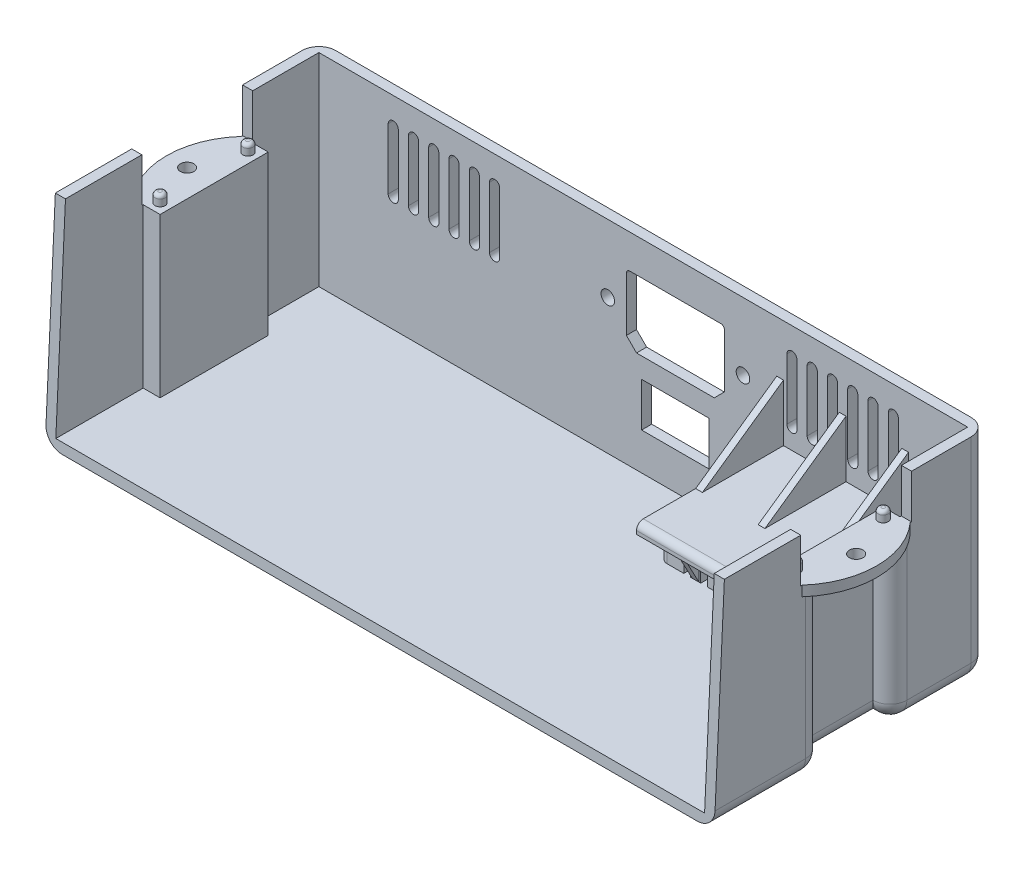
SolidWorks part; units mm, degrees
ref_plane "Alzado" through (0, 0, 0) normal (0, 0, 1) x (1, 0, 0)
ref_plane "Planta" through (0, 0, 0) normal (0, 1, 0) x (1, 0, 0)
ref_plane "Vista lateral" through (0, 0, 0) normal (1, 0, 0) x (0, 0, -1)
sketch "Croquis1" plane through (0, 0, 0) normal (0, 1, 0) x (1, 0, 0)
  line L0 (99, -10) -> (94, -10)
  line L1 (-99, 39) -> (99, 39)
  line L2 (-99, 39) -> (-99, 10)
  line L3 (-99, -42) -> (99, -42)
  line L4 (99, 39) -> (99, 10)
  line L5 (94, -10) -> (94, 10)
  line L6 (94, 10) -> (99, 10)
  line L7 (99, -10) -> (99, -42)
  line L8 (-99, 10) -> (-94, 10)
  line L9 (-94, 10) -> (-94, -10)
  line L10 (-94, -10) -> (-99, -10)
  line L11 (-99, -10) -> (-99, -42)
  point P4 (0, -42)
  point P7 (94, 0)
  point P14 (-94, 0)
  dimension "D1" = 81
  dimension "D2" = 198
  dimension "D3" = 39
  dimension "D4" = 5
  dimension "D5" = 20
  dimension "D6" = 20
  dimension "D7" = 5
extrude "Saliente-Extruir1" add sketch "Croquis1" along normal blind 3
sketch "Croquis2" plane through (0, 3, 0) normal (0, 1, 0) x (1, 0, 0)
  line L3 (96, 36) -> (-96, 36)
  line L4 (-96, 36) -> (-96, 16)
  line L6 (-99, 10) -> (-99, 39)
  line L7 (-99, 39) -> (99, 39)
  line L8 (99, 39) -> (99, 10)
  line L9 (-96, 16) -> (-91, 16)
  line L10 (-91, 16) -> (-91, -16)
  line L11 (-91, -16) -> (-96, -16)
  line L12 (-94, -10) -> (-99, -10)
  line L13 (-94, -10) -> (-94, 10)
  line L14 (-94, 10) -> (-99, 10)
  line L17 (91, 16) -> (96, 16)
  line L18 (91, 16) -> (91, -16)
  line L19 (91, -16) -> (96, -16)
  line L20 (96, 16) -> (96, 36)
  line L21 (99, 10) -> (94, 10)
  line L22 (94, 10) -> (94, -10)
  line L23 (94, -10) -> (99, -10)
  line L25 (96, -16) -> (96, -42)
  line L26 (-99, -42) -> (99, -42) construction
  line L27 (96, -42) -> (99, -42)
  line L28 (99, -42) -> (99, -10)
  line L29 (-96, -16) -> (-96, -42)
  line L30 (-96, -42) -> (-99, -42)
  line L31 (-99, -42) -> (-99, -10)
  dimension "D3" = 3
  dimension "D4" = 6
  dimension "D5" = 3
  dimension "D6" = 6
  dimension "D7" = 3
  dimension "D8" = 6
  dimension "D9" = 6
  dimension "D2" = 3
  dimension "D10" = 3
  dimension "D11" = 3
extrude "Saliente-Extruir2" add sketch "Croquis2" along normal blind 60
sketch "Croquis5" plane through (99, 0, 0) normal (1, 0, 0) x (0, 0, -1)
  line L2 (-42, 63) -> (-10, 63) construction
  line L3 (-39, 63) -> (-42, 63)
  line L5 (-42, 0) -> (-39, 63)
  line L6 (-42, 0) -> (-42, 63)
  dimension "D1" = 3
extrude "Cortar-Extruir2" cut sketch "Croquis5" against normal up to surface (198 mm away) up to face at (-99, 31.5, 26)
sketch "Croquis7" plane through (0, 63, 0) normal (0, 1, 0) x (1, 0, 0)
  line L0 (-91, -16) -> (-99, -16)
  line L1 (-99, -10) -> (-99, -39) construction
  line L2 (-99, -16) -> (-99, -10)
  line L3 (-99, -10) -> (-94, -10)
  line L4 (-94, -10) -> (-94, 10)
  line L5 (-94, 10) -> (-99, 10)
  line L6 (-99, 10) -> (-99, 16)
  line L7 (-99, 39) -> (-99, 10) construction
  line L8 (-99, 16) -> (-91, 16)
  line L9 (-91, 16) -> (-91, -16)
  line L10 (91, 16) -> (99, 16)
  line L11 (99, 10) -> (99, 39) construction
  line L12 (99, 16) -> (99, 10)
  line L13 (99, 10) -> (94, 10)
  line L14 (94, 10) -> (94, -10)
  line L15 (94, -10) -> (99, -10)
  line L16 (99, -10) -> (99, -16)
  line L17 (99, -39) -> (99, -10) construction
  line L18 (99, -16) -> (91, -16)
  line L20 (91, -16) -> (91, 16)
extrude "Cortar-Extruir3" cut sketch "Croquis7" against normal blind 16
sketch "Croquis8" plane through (0, 47, 0) normal (0, 1, 0) x (1, 0, 0)
  line L0 (-99, -16) -> (-91, -16)
  line L1 (-91, -16) -> (-91, 16)
  line L2 (-91, 16) -> (-99, 16)
  line L3 (99, -16) -> (91, -16)
  line L4 (91, -16) -> (91, 16)
  line L5 (91, 16) -> (99, 16)
  arc A0 (-99, -16) -> (-99, 16) centre (-81.1115, 0) cw
  arc A1 (99, -16) -> (99, 16) centre (81.1115, 0) ccw
  dimension "D1" = 24
  dimension "D2" = 24
extrude "Saliente-Extruir3" add sketch "Croquis8" along normal blind 3
sketch "Croquis9" plane through (0, 50, 0) normal (0, 1, 0) x (1, 0, 0)
  line L0 (-91, -16) -> (-91, 16) construction
  line L1 (91, 16) -> (91, -16) construction
  circle A0 centre (-99, 0) radius 2
  circle A1 centre (99, 0) radius 2
  dimension "D2" = 4
  dimension "D4" = 4
  dimension "D1" = 8
  dimension "D3" = 8
extrude "Cortar-Extruir4" cut sketch "Croquis9" against normal up to surface (3 mm away) up to face at (98.3519, 47, 0)
fillet "Redondeo1" radius 5 17 edges at (-99, 0, -24.5) (99, 0, -24.5) (-99, 31.5, -39) (99, 31.5, -39) (0, 0, -39) (99, 0, 26) (96.5, 0, 10) (94, 0, 0) (96.5, 0, -10) (-96.5, 0, -10) (-94, 0, 0) (-96.5, 0, 10) (-99, 0, 26) (99, 23.5, 10) (99, 23.5, -10) (-99, 23.5, 10) (-99, 23.5, -10)
sketch "Croquis10" plane through (0, 50, 0) normal (0, 1, 0) x (1, 0, 0)
  line L0 (96, 16) -> (91, 16) construction
  line L1 (91, 16) -> (91, -16) construction
  line L2 (91, -16) -> (96, -16) construction
  line L3 (-91, 16) -> (-96, 16) construction
  line L4 (-91, -16) -> (-91, 16) construction
  line L5 (-96, -16) -> (-91, -16) construction
  circle A0 centre (94, 13) radius 1.5
  circle A1 centre (94, -13) radius 1.5
  circle A2 centre (-94, 13) radius 1.5
  circle A3 centre (-94, -13) radius 1.5
  dimension "D1" = 3
  dimension "D3" = 3
  dimension "D5" = 3
  dimension "D7" = 3
  dimension "D6" = 3
  dimension "D9" = 3
  dimension "D10" = 3
  dimension "D2" = 3
  dimension "D4" = 3
  dimension "D8" = 3
  dimension "D11" = 3
  dimension "D12" = 3
extrude "Saliente-Extruir4" add sketch "Croquis10" along normal blind 3
fillet "Redondeo3" radius 1 4 edges at (-94, 53, 14.5) (-94, 53, -11.5) (94, 53, -11.5) (94, 53, 14.5)
sketch "Croquis11" plane through (0, 0, -39) normal (0, 0, -1) x (-1, 0, 0)
  line L0 (-72.5, 37) -> (-72.5, 55)
  line L1 (-75.5, 37) -> (-75.5, 55)
  line L2 (-94, 63) -> (94, 63) construction
  line L3 (-94, 63) -> (-94, 5) construction
  line L12 (-69.5, 37) -> (-69.5, 55)
  line L13 (-66.5, 37) -> (-66.5, 55)
  line L14 (-63.5, 37) -> (-63.5, 55)
  line L15 (-60.5, 37) -> (-60.5, 55)
  line L16 (-57.5, 37) -> (-57.5, 55)
  line L17 (-54.5, 37) -> (-54.5, 55)
  line L18 (-51.5, 37) -> (-51.5, 55)
  line L19 (-48.5, 37) -> (-48.5, 55)
  line L20 (-45.5, 37) -> (-45.5, 55)
  line L21 (-42.5, 37) -> (-42.5, 55)
  line L22 (0, 5) -> (0, 63) construction
  line L23 (-94, 5) -> (94, 5) construction
  line L24 (42.5, 37) -> (42.5, 55)
  line L25 (45.5, 37) -> (45.5, 55)
  line L26 (48.5, 37) -> (48.5, 55)
  line L27 (51.5, 37) -> (51.5, 55)
  line L28 (54.5, 37) -> (54.5, 55)
  line L29 (57.5, 37) -> (57.5, 55)
  line L30 (60.5, 37) -> (60.5, 55)
  line L31 (63.5, 37) -> (63.5, 55)
  line L32 (66.5, 37) -> (66.5, 55)
  line L33 (69.5, 37) -> (69.5, 55)
  line L34 (72.5, 37) -> (72.5, 55)
  line L35 (75.5, 37) -> (75.5, 55)
  arc A0 (-72.5, 37) -> (-75.5, 37) centre (-74, 37) cw
  arc A1 (-72.5, 55) -> (-75.5, 55) centre (-74, 55) ccw
  arc A10 (-66.5, 55) -> (-69.5, 55) centre (-68, 55) ccw
  arc A11 (-66.5, 37) -> (-69.5, 37) centre (-68, 37) cw
  arc A12 (-60.5, 55) -> (-63.5, 55) centre (-62, 55) ccw
  arc A13 (-60.5, 37) -> (-63.5, 37) centre (-62, 37) cw
  arc A14 (-54.5, 55) -> (-57.5, 55) centre (-56, 55) ccw
  arc A15 (-54.5, 37) -> (-57.5, 37) centre (-56, 37) cw
  arc A16 (-48.5, 55) -> (-51.5, 55) centre (-50, 55) ccw
  arc A17 (-48.5, 37) -> (-51.5, 37) centre (-50, 37) cw
  arc A18 (-42.5, 55) -> (-45.5, 55) centre (-44, 55) ccw
  arc A19 (-42.5, 37) -> (-45.5, 37) centre (-44, 37) cw
  arc A20 (42.5, 37) -> (45.5, 37) centre (44, 37) ccw
  arc A21 (42.5, 55) -> (45.5, 55) centre (44, 55) cw
  arc A22 (48.5, 37) -> (51.5, 37) centre (50, 37) ccw
  arc A23 (48.5, 55) -> (51.5, 55) centre (50, 55) cw
  arc A24 (54.5, 37) -> (57.5, 37) centre (56, 37) ccw
  arc A25 (54.5, 55) -> (57.5, 55) centre (56, 55) cw
  arc A26 (60.5, 37) -> (63.5, 37) centre (62, 37) ccw
  arc A27 (60.5, 55) -> (63.5, 55) centre (62, 55) cw
  arc A28 (66.5, 37) -> (69.5, 37) centre (68, 37) ccw
  arc A29 (66.5, 55) -> (69.5, 55) centre (68, 55) cw
  arc A30 (72.5, 37) -> (75.5, 37) centre (74, 37) ccw
  arc A31 (72.5, 55) -> (75.5, 55) centre (74, 55) cw
  dimension "D6" = 6
  dimension "D1" = 1.5
  dimension "D5" = 1.5
  dimension "D2" = 18
  dimension "D3" = 8
  dimension "D4" = 20
extrude "Cortar-Extruir5" cut sketch "Croquis11" against normal up to surface (3 mm away) up to face at (0, 33, -36)
sketch "Croquis13" plane through (0, 0, -39) normal (0, 0, -1) x (-1, 0, 0)
  line L0 (4, 53) -> (-23, 53)
  line L5 (5, 36) -> (5, 52)
  line L6 (-94, 63) -> (94, 63) construction
  line L8 (2, 33) -> (-21, 33)
  line L9 (-24, 36) -> (-24, 52)
  line L10 (10.5, 43) -> (-29.5, 43) construction
  line L11 (-9.5, 33) -> (-9.5, 53) construction
  line L12 (5, 36) -> (2, 33)
  line L13 (0.5, 14) -> (-19.5, 14)
  line L14 (0.5, 14) -> (0.5, 27)
  line L15 (0.5, 27) -> (-19.5, 27)
  line L16 (-19.5, 14) -> (-19.5, 27)
  line L17 (-21, 33) -> (-24, 36)
  circle A1 centre (-29.5, 43) radius 2
  circle A2 centre (10.5, 43) radius 2
  arc A3 (-42.5, 55) -> (-45.5, 55) centre (-44, 55) ccw construction
  arc A4 (4, 53) -> (5, 52) centre (4, 52) cw
  arc A5 (-23, 53) -> (-24, 52) centre (-23, 52) ccw
  point P13 (-9.5, 43)
  point P16 (-9.5, 43)
  point P21 (-9.5, 27)
  point P26 (5, 53)
  point P29 (-24, 53)
  dimension "D4" = 4
  dimension "D5" = 4
  dimension "D6" = 20
  dimension "D17" = 1
  dimension "D2" = 20
  dimension "D3" = 40
  dimension "D7" = 10
  dimension "D8" = 13
  dimension "D9" = 20
  dimension "D10" = 6
  dimension "D11" = 17
  dimension "D12" = 45
  dimension "D13" = 17
  dimension "D14" = 45
  dimension "D15" = 10
  dimension "D16" = 29
extrude "Cortar-Extruir6" cut sketch "Croquis13" against normal up to surface (3 mm away) up to face at (74, 46, -36)
sketch "Croquis15" plane through (0, 0, -39) normal (0, 0, -1) x (-1, 0, 0)
  line L0 (24.5, 18.5) -> (4.5, 18.5) construction
  line L1 (0.5, 14) -> (0.5, 27) construction
  line L3 (-19.5, 14) -> (0.5, 14) construction
  text T0 "POWER \r\nON" font "Century Gothic" height in points 14
  dimension "D1" = 4
  dimension "D2" = 20
  dimension "D3" = 4.5
extrude "Cortar-Extruir7" cut sketch "Croquis15" against normal blind 1
sketch "Croquis16" plane through (0, 0, -36) normal (0, 0, 1) x (1, 0, 0)
  line L0 (62, 37) -> (56, 37) construction
  line L1 (78.5, 28) -> (39.5, 28)
  line L2 (78.5, 28) -> (78.5, 31)
  line L3 (78.5, 31) -> (39.5, 31)
  line L4 (39.5, 28) -> (39.5, 31)
  line L5 (-96, 3) -> (96, 3) construction
  point P8 (59, 31)
  point P9 (59, 37)
  dimension "D2" = 3
  dimension "D1" = 39
  dimension "D3" = 25
extrude "Saliente-Extruir5" add sketch "Croquis16" along normal blind 34.5
sketch "Croquis19" plane through (0, 28, 0) normal (0, -1, 0) x (1, 0, 0)
  line L1 (39.5, -36) -> (78.5, -36) construction
  line L6 (61.5, -4.5) -> (74.5, -4.5)
  line L9 (78.5, -17.5) -> (78.5, -1.5)
  line L10 (78.5, -1.5) -> (39.5, -1.5)
  line L11 (61.5, -4.5) -> (61.5, -8.5)
  line L12 (39.5, -1.5) -> (39.5, -17.5)
  line L14 (39.5, -1.5) -> (78.5, -1.5) construction
  line L15 (42.5, -17.5) -> (42.5, -8.5)
  line L16 (43.5, -4.5) -> (56.5, -4.5)
  line L17 (57.5, -8.5) -> (57.5, -36)
  line L18 (75.5, -8.5) -> (75.5, -17.5)
  line L19 (61.5, -8.5) -> (60.5, -8.5)
  line L20 (57.5, -8.5) -> (56.5, -8.5)
  line L21 (56.5, -8.5) -> (56.5, -4.5)
  line L22 (42.5, -8.5) -> (43.5, -8.5)
  line L23 (43.5, -8.5) -> (43.5, -4.5)
  line L24 (75.5, -8.5) -> (74.5, -8.5)
  line L25 (74.5, -8.5) -> (74.5, -4.5)
  line L26 (60.5, -8.5) -> (60.5, -36)
  line L27 (60.5, -36) -> (57.5, -36)
  line L28 (42.5, -17.5) -> (39.5, -17.5)
  line L29 (78.5, -17.5) -> (75.5, -17.5)
  dimension "D1" = 3
  dimension "D3" = 3
  dimension "D5" = 3
  dimension "D2" = 3
  dimension "D4" = 15
  dimension "D6" = 15
  dimension "D7" = 1
  dimension "D8" = 4
  dimension "D9" = 4
  dimension "D10" = 1
  dimension "D11" = 4
  dimension "D12" = 1
  dimension "D14" = 1
  dimension "D13" = 16
  dimension "D15" = 16
extrude "Saliente-Extruir6" add sketch "Croquis19" along normal blind 10
ref_plane "Plano1" through (59, 0, 0) normal (-1, 0, 0) x (0, 0, 1)
sketch "Croquis20" plane through (59, 0, 0) normal (-1, 0, 0) x (0, 0, 1)
  line L0 (-12, 31) -> (-36, 47.805)
  line L1 (-36, 31) -> (-36, 28) construction
  line L2 (-1.5, 31) -> (-36, 31) construction
  line L3 (-36, 37) -> (-36, 55) construction
  dimension "D1" = 35
  dimension "D2" = 24
rib "Nervio1" sketch "Croquis20" sketch "Croquis20" thickness 2 extrusion direction parallel to sketch draft on no parameters "D1"=2
pattern_linear "MatrizL1" count 2 spacing 18.5 along (-1, 0, 0) count 2 spacing 18.5 along (1, 0, 0) of "Nervio1"
sketch "Croquis21" plane through (0, 0, -1.5) normal (0, 0, 1) x (1, 0, 0)
  line L0 (71.5, 18) -> (71.5, 24)
  line L1 (78.5, 18) -> (39.5, 18) construction
  line L2 (69.5, 24) -> (69.5, 18)
  line L3 (71.5, 18) -> (69.5, 18)
  line L4 (78.5, 18) -> (78.5, 31) construction
  line L5 (66.5, 18) -> (64.5, 18)
  line L6 (64.5, 24) -> (64.5, 18)
  line L7 (66.5, 18) -> (66.5, 24)
  line L8 (71.5, 18) -> (66.5, 18) construction
  line L9 (53.5, 18) -> (51.5, 18)
  line L10 (51.5, 24) -> (51.5, 18)
  line L11 (53.5, 18) -> (53.5, 24)
  line L12 (48.5, 18) -> (46.5, 18)
  line L13 (46.5, 24) -> (46.5, 18)
  line L14 (48.5, 18) -> (48.5, 24)
  line L15 (71.5, 18) -> (53.5, 18) construction
  line L16 (39.5, 31) -> (39.5, 18) construction
  arc A0 (71.5, 24) -> (69.5, 24) centre (70.5, 24) ccw
  arc A1 (66.5, 24) -> (64.5, 24) centre (65.5, 24) ccw
  arc A2 (53.5, 24) -> (51.5, 24) centre (52.5, 24) ccw
  arc A3 (48.5, 24) -> (46.5, 24) centre (47.5, 24) ccw
  dimension "D5" = 3
  dimension "D1" = 2
  dimension "D2" = 7
  dimension "D3" = 6
  dimension "D7" = 7
extrude "Cortar-Extruir8" cut sketch "Croquis21" against normal up to surface (3 mm away) up to face at (50, 23, -4.5)
sketch "Croquis22" plane through (0, 0, -39) normal (0, 0, -1) x (-1, 0, 0)
  line L0 (-56, 37) -> (-62, 37) construction
  line L1 (-50, 21.5) -> (-68, 21.5) construction
  circle A0 centre (-50, 21.5) radius 5
  circle A1 centre (-68, 21.5) radius 5
  arc A2 (-51.5, 37) -> (-48.5, 37) centre (-50, 37) ccw construction
  point P7 (-50, 35.5)
  point P8 (-59, 21.5)
  point P13 (-59, 37)
  dimension "D1" = 10
  dimension "D2" = 10
  dimension "D3" = 14
  dimension "D4" = 18
extrude "Cortar-Extruir9" cut sketch "Croquis22" against normal up to surface (3 mm away) up to face at (59, 34.9269, -36)
sketch "Croquis23" plane through (0, 0, -1.5) normal (0, 0, 1) x (1, 0, 0)
  line L0 (78.5, 18) -> (78.5, 31) construction
  line L1 (39.5, 31) -> (78.5, 31)
  line L2 (39.5, 31) -> (39.5, 28)
  line L3 (39.5, 28) -> (78.5, 28)
  line L4 (78.5, 31) -> (78.5, 28)
  dimension "D1" = 3
extrude "Saliente-Extruir7" add sketch "Croquis23" along normal blind 7
ref_plane "Plano2" through (68, 0, 0) normal (-1, 0, 0) x (0, 0, 1)
sketch "Croquis27" plane through (68, 0, 0) normal (-1, 0, 0) x (0, 0, 1)
  line L0 (-1.5, 18) -> (3.8171, 28)
  line L1 (5.5, 28) -> (-1.5, 28) construction
  line L2 (-1.5, 28) -> (-1.5, 18) construction
  dimension "D1" = 28
rib "Nervio5" sketch "Croquis27" sketch "Croquis27" thickness 2 extrusion direction parallel to sketch draft on no parameters "D1"=2
pattern_linear "MatrizL2" count 2 spacing 18 along (-1, 0, 0) of "Nervio5"
fillet "Redondeo4" radius 2 3 edges at (78.5, 23, -1.5) (39.5, 23, -1.5) (59, 31, 5.5)
sketch "Croquis28" plane through (0, 63, 0) normal (0, 1, 0) x (1, 0, 0)
  line L0 (-96, 16) -> (-96, 36) construction
  line L1 (-99, 16) -> (-96, 16)
  line L2 (-99, 16) -> (-99, 16.4)
  line L3 (-99, 16.4) -> (-96, 16.4)
  line L4 (-96, 16) -> (-96, 16.4)
  line L5 (-96, -41.8571) -> (-96, -16) construction
  line L6 (-99, -16) -> (-96, -16)
  line L7 (-99, -16) -> (-99, -16.4)
  line L8 (-99, -16.4) -> (-96, -16.4)
  line L9 (-96, -16) -> (-96, -16.4)
  line L10 (96, -16) -> (96, -41.8571) construction
  line L11 (99, -16) -> (96, -16)
  line L12 (99, -16) -> (99, -16.4)
  line L13 (99, -16.4) -> (96, -16.4)
  line L14 (96, -16) -> (96, -16.4)
  line L15 (96, 36) -> (96, 16) construction
  line L16 (99, 16) -> (96, 16)
  line L17 (99, 16) -> (99, 16.4)
  line L18 (99, 16.4) -> (96, 16.4)
  line L19 (96, 16) -> (96, 16.4)
  dimension "D1" = 0.4
  dimension "D2" = 0.4
  dimension "D3" = 0.4
  dimension "D4" = 0.4
extrude "Cortar-Extruir10" cut sketch "Croquis28" against normal up to surface (13 mm away) up to face at (94, 50, 14.5)
equation "\"grosor\"=3"
equation "\"D1@Saliente-Extruir1\"=\"grosor\""
equation "\"D3@Croquis2\"= \"grosor\""
equation "\"D4@Croquis2\"=2 * \"grosor\""
equation "\"D5@Croquis2\"=\"grosor\""
equation "\"D6@Croquis2\"=2 * \"grosor\""
equation "\"D7@Croquis2\"=\"grosor\""
equation "\"D8@Croquis2\"=2 * \"grosor\""
equation "\"D9@Croquis2\"=2 * \"grosor\""
equation "\"D2@Croquis2\"=\"grosor\""
equation "\"D10@Croquis2\"=\"grosor\""
equation "\"D11@Croquis2\"=\"grosor\""
equation "\"D1@Croquis5\"=\"grosor\""
equation "\"D1@Saliente-Extruir3\"=\"grosor\""
equation "\"D1@Croquis10\"=\"grosor\""
equation "\"D3@Croquis10\"=\"grosor\""
equation "\"D2@Croquis10\"=\"grosor\""
equation "\"D4@Croquis10\"=\"grosor\""
equation "\"D5@Croquis10\"=\"grosor\""
equation "\"D6@Croquis10\"=\"grosor\""
equation "\"D7@Croquis10\"=\"grosor\""
equation "\"D8@Croquis10\"=\"grosor\""
equation "\"D9@Croquis10\"=\"grosor\""
equation "\"D10@Croquis10\"=\"grosor\""
equation "\"D11@Croquis10\"=\"grosor\""
equation "\"D12@Croquis10\"=\"grosor\""
equation "\"D1@Saliente-Extruir4\"=\"grosor\""
equation "\"D1@Croquis11\"=\"grosor\" /2"
equation "\"ancho_externo\"=81"
equation "\"D1@Croquis1\"=\"ancho_externo\""
equation "\"D3@Croquis1\"=(\"ancho_externo\"-3)/2"
equation "\"D2@Croquis16\"=\"grosor\""
equation "\"D1@Croquis19\"=\"grosor\""
equation "\"D2@Croquis19\"=\"grosor\""
equation "\"D3@Croquis19\"=\"grosor\""
equation "\"D5@Croquis19\"=\"grosor\""
equation "\"D7@Croquis21\"=\"grosor\"+4"
equation "\"D2@Croquis21\"=\"grosor\"+4"
